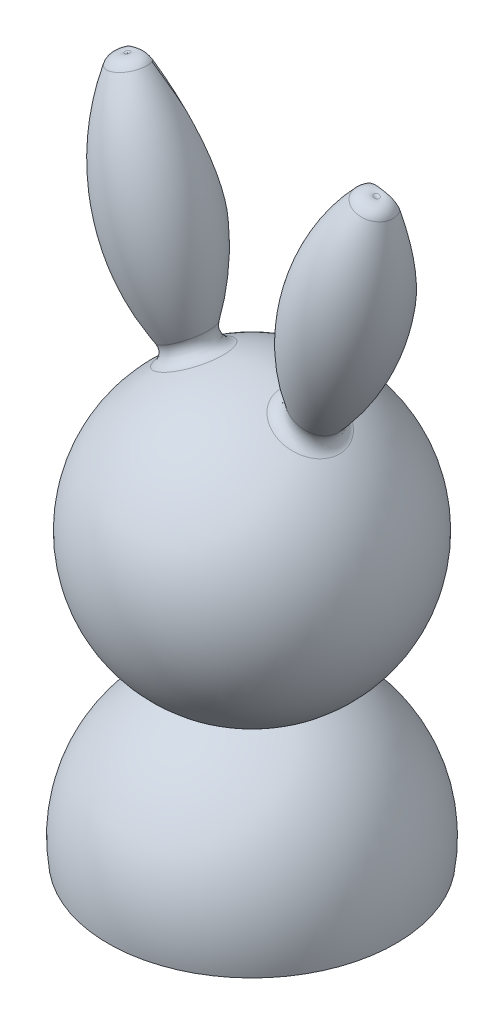
SolidWorks part; units mm, degrees
ref_plane "Front Plane" through (0, 0, 0) normal (0, 0, 1) x (1, 0, 0)
ref_plane "Top Plane" through (0, 0, 0) normal (0, 1, 0) x (1, 0, 0)
ref_plane "Right Plane" through (0, 0, 0) normal (1, 0, 0) x (0, 0, -1)
sketch "Sketch1" plane through (0, 0, 0) normal (1, 0, 0) x (0, 0, -1)
  line L0 (0, 27.2621) -> (0, 0) construction
  line L1 (0, 27.2621) -> (0, 0)
  line L2 (0, 0) -> (23.5613, 0)
  arc A0 (23.5613, 0) -> (0, 27.2621) centre (0, 3.4496) ccw
revolve "Revolve3" add sketch "Sketch1" angle 360 about L0
sketch "Sketch2" plane through (0, 0, 0) normal (0, 0, 1) x (1, 0, 0)
  line L0 (0, 69.85) -> (0, 23.8125) construction
  line L1 (-23.5613, 0) -> (23.5613, 0) construction
  line L2 (0, 69.85) -> (0, 23.8125)
  arc A0 (0, 23.8125) -> (0, 69.85) centre (0, 46.8312) ccw
  dimension "D1" = 69.85
revolve "Revolve4" add sketch "Sketch2" angle 360 about L0
sketch "Sketch3" plane through (0, 0, 0) normal (0, 0, 1) x (1, 0, 0)
  line L0 (9.4417, 63.5) -> (20.3957, 104.3808) construction
  line L1 (-27.0422, 68.2126) -> (30.381, 68.2126) construction
  line L2 (9.4417, 63.5) -> (20.3957, 104.3808)
  line L3 (20.3957, 104.3808) -> (22.6097, 104.3808)
  arc A0 (9.4417, 63.5) -> (22.6097, 104.3808) centre (-13.8145, 93.5522) ccw
  dimension "D1" = 75
revolve "Revolve5" add sketch "Sketch3" angle 360 about L2
fillet "Fillet2" radius 2.3 1 edges at (22.6097, 104.3808, 0)
fillet "Fillet3" radius 2 1 edges at (10.1122, 67.3489, 2.5752)
mirror "Mirror1" about plane through (0, 0, 0) normal (1, 0, 0) of "Revolve5", "Fillet2", "Fillet3"
sketch "Sketch4" plane through (0, 0, 0) normal (1, 0, 0) x (0, 0, -1)
  line L0 (0, 110.2134) -> (8.613, 70.3525)
  line L1 (8.613, 70.3525) -> (14.401, 71.6031)
  line L2 (14.401, 71.6031) -> (5.7879, 111.4641)
  line L3 (5.7879, 111.4641) -> (0, 110.2134)
extrude "Cut-Extrude1" cut sketch "Sketch4" against normal through all both and the other way through all
